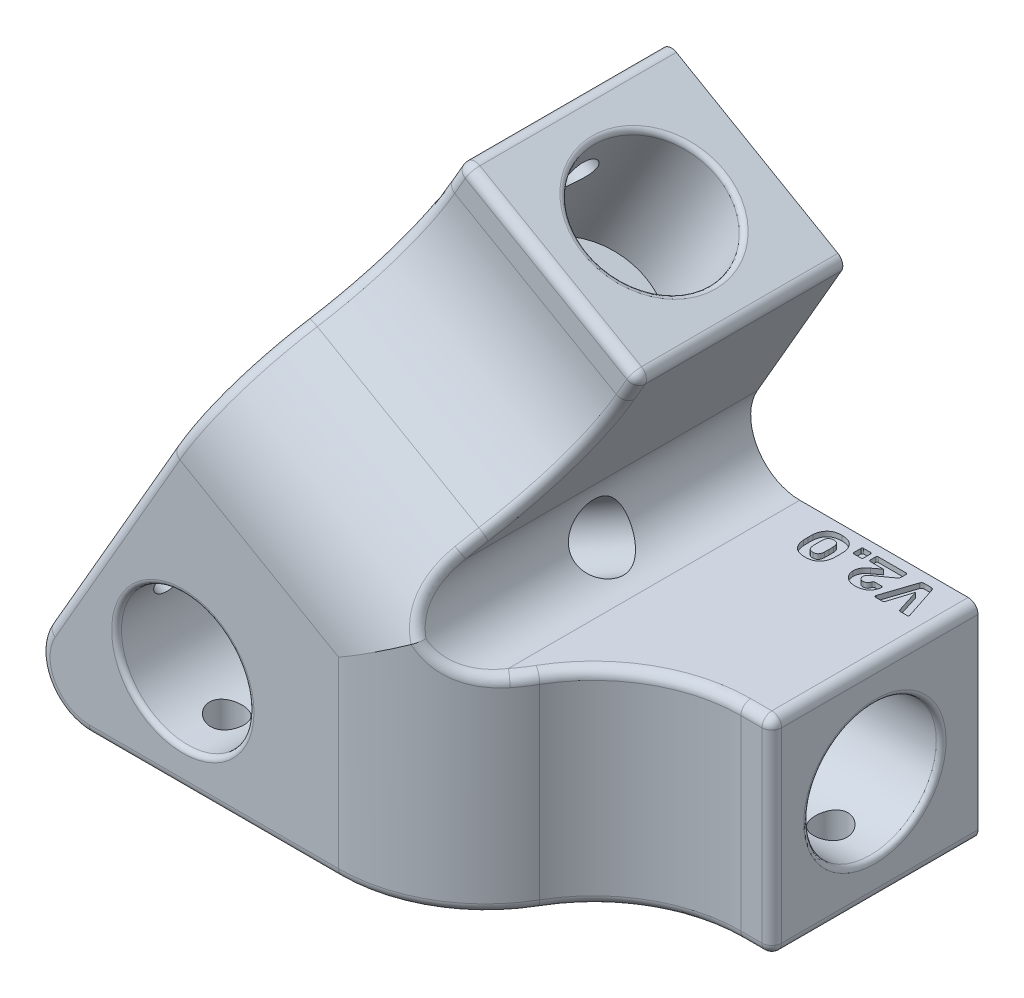
SolidWorks part; units mm, degrees
other "Corner Joint"
ref_plane "Front Plane" through (0, 0, 0) normal (0, 0, 1) x (1, 0, 0)
ref_plane "Top Plane" through (0, 0, 0) normal (0, 1, 0) x (1, 0, 0)
ref_plane "Right Plane" through (0, 0, 0) normal (1, 0, 0) x (0, 0, -1)
sketch "Sketch1" plane through (0, 0, 0) normal (0, 0, 1) x (1, 0, 0)
  line L0 (0, 0) -> (45, 0) construction
  line L1 (0, 0) -> (22.5, 38.9711) construction
  line L16 (45, -10.5) -> (-9.5263, -10.5)
  line L17 (16.8708, 42.2211) -> (28.1292, 35.7211) construction
  line L18 (16.8708, 42.2211) -> (9.3708, 29.2308) construction
  line L19 (9.3708, 29.2308) -> (20.6292, 22.7308) construction
  line L20 (28.1292, 35.7211) -> (20.6292, 22.7308) construction
  line L21 (30, 6.5) -> (45, 6.5) construction
  line L22 (30, 6.5) -> (30, -6.5) construction
  line L23 (30, -6.5) -> (45, -6.5) construction
  line L24 (45, 6.5) -> (45, -6.5) construction
  line L25 (-13.8564, -3) -> (13.4067, 44.2211)
  line L26 (13.4067, 44.2211) -> (31.5933, 33.7211)
  line L27 (31.5933, 33.7211) -> (22.5167, 18)
  line L28 (26.8468, 10.5) -> (45, 10.5)
  line L29 (45, 10.5) -> (45, -10.5)
  circle A0 centre (0, 0) radius 6.5 construction
  arc A1 (26.8468, 10.5) -> (22.5167, 18) centre (26.8468, 15.5) cw
  arc A2 (-9.5263, -10.5) -> (-13.8564, -3) centre (-9.5263, -5.5) cw
  point P2 (22.5, 38.9711)
  point P12 (45, 0)
  dimension "D7" = 15
  dimension "D8" = 13
  dimension "D13" = 5
  dimension "D1" = 60
  dimension "D2" = 45
  dimension "D3" = 45
  dimension "D4" = 13
  dimension "D5" = 15
  dimension "D6" = 13
  dimension "D9" = 4
  dimension "D10" = 4
  dimension "D11" = 4
  dimension "D12" = 4
extrude "Boss-Extrude3" add sketch "Sketch1" along normal blind 21
sketch "Sketch3" plane through (0, 0, 21) normal (0, 0, 1) x (1, 0, 0)
  line L0 (22.5167, 18) -> (4.3301, 28.5)
  line L1 (-13.8564, -3) -> (13.4067, 44.2211) construction
  line L2 (26.8468, 10.5) -> (26.8468, -10.5)
  line L3 (45, -10.5) -> (-9.5263, -10.5) construction
  line L4 (13.4067, 44.2211) -> (31.5933, 33.7211) construction
  line L5 (4.3301, 28.5) -> (-13.8564, -3)
  line L6 (-9.5263, -10.5) -> (26.8468, -10.5)
  line L7 (26.8468, 10.5) -> (26.6736, 10.5)
  line L8 (22.4301, 17.85) -> (22.5167, 18)
  line L9 (31.5933, 33.7211) -> (22.5167, 18) construction
  line L10 (26.8468, 10.5) -> (45, 10.5) construction
  circle A0 centre (0, 0) radius 6.75
  arc A1 (-9.5263, -10.5) -> (-13.8564, -3) centre (-9.5263, -5.5) cw
  arc A3 (22.5167, 18) -> (26.8468, 10.5) centre (26.8468, 15.5) ccw
  arc M12 (26.8468, 10.5) -> (22.5167, 18) centre (26.8468, 15.5) cw
  line M15 (13.4067, 44.2211) -> (-13.8564, -3)
  arc M16 (-13.8564, -3) -> (-9.5263, -10.5) centre (-9.5263, -5.5) ccw
  line M17 (-9.5263, -10.5) -> (45, -10.5)
  dimension "D1" = 5
  dimension "D2" = 13.5
extrude "Boss-Extrude4" add sketch "Sketch3" along normal blind 15 contours L2 L0 A0 M12 M15 M16 M17 region at (9.2242, 5.3256, 21)
sketch "Sketch4" plane through (45, 0, 0) normal (1, 0, 0) x (0, 0, -1)
  line L0 (-21, -10.5) -> (-21, 10.5) construction
  line L1 (-21, -10.5) -> (0, -10.5) construction
  circle A0 centre (-10.5, 0) radius 6.75
  dimension "D1" = 13.5
  dimension "D2" = 10.5
  dimension "D3" = 10.5
extrude "Cut-Extrude1" cut sketch "Sketch4" against normal blind 15
sketch "Sketch5" plane through (22.5, 38.9711, 0) normal (0.5, 0.866, 0) x (0.866, -0.5, 0)
  line L0 (-10.5, -21) -> (-10.5, 0) construction
  line L1 (10.5, 0) -> (-10.5, 0) construction
  circle A0 centre (0, -10.5) radius 6.75
  dimension "D1" = 13.5
  dimension "D2" = 10.5
  dimension "D3" = 10.5
extrude "Cut-Extrude2" cut sketch "Sketch5" against normal blind 15
fillet "Fillet1" radius 15 2 edges at (13.4234, 23.25, 21) (26.8468, 0, 21)
fillet "Fillet2" radius 15 2 edges at (26.8468, 0, 36) (13.4234, 23.25, 36)
fillet "Fillet3" radius 1 23 edges at (24.1108, 11.315, 33.5309) (27.9284, 10.5, 29.9162) (43.4234, 10.5, 21) (30.805, 32.3558, 21) (21.8979, 16.2133, 32.906) (23.0575, 18.9367, 29.9162) (43.4234, -10.5, 21) (34.3468, -10.5, 23.0096) (23.366, -10.5, 33.9904) (3.1699, -10.5, 36) (-13.8564, -8, 36) (-7.5083, 7.9952, 36) (2.5897, 25.4856, 33.9904) (12.6184, 42.8558, 21) (45, -10.5, 10.5) (45, 10.5, 10.5) (45, 0, 21) (34.3468, 10.5, 23.0096) (31.5933, 33.7211, 10.5) (22.5, 38.9711, 21) (26.2667, 24.4952, 23.0096) (8.0801, 34.9952, 23.0096) (13.4067, 44.2211, 10.5)
fillet "Fillet4" radius 0.5 3 edges at (45, 6.75, 10.5) (16.6543, 42.3461, 10.5) (6.75, 0, 36)
sketch "Sketch7" plane through (0, -10.5, 0) normal (0, -1, 0) x (1, 0, 0)
  line L0 (45, 20) -> (45, 0) construction
  line L1 (-9.5263, 36) -> (15.866, 36) construction
  line L2 (-14.5263, 35) -> (-14.5263, 0) construction
  circle A0 centre (40, 10) radius 1.75
  circle A1 centre (-0.5263, 31) radius 1.75
  point P4 (45, 10)
  dimension "D1" = 3.5
  dimension "D2" = 5
  dimension "D3" = 5
  dimension "D4" = 14
extrude "Cut-Extrude4" cut sketch "Sketch7" against normal blind 14
sketch "Sketch8" plane through (-9.0933, 5.25, 0) normal (-0.866, 0.5, 0) x (0, 0, 1)
  line L0 (0, 45) -> (20, 45) construction
  line L1 (0, -14.5263) -> (35, -14.5263) construction
  line L2 (36, -13.5263) -> (36, -9.5263) construction
  circle A0 centre (10, 40) radius 1.75
  circle A1 centre (31, -0.5263) radius 1.75
  point P5 (10, 45)
  dimension "D1" = 3.5
  dimension "D2" = 5
  dimension "D3" = 14
  dimension "D4" = 5
extrude "Cut-Extrude5" cut sketch "Sketch8" against normal blind 10
sketch "Sketch9" plane through (0, 0, 36) normal (0, 0, 1) x (1, 0, 0)
  line L0 (-4.0981, 1.0981) -> (-1.0981, -4.0981)
  line L1 (-1.0981, -4.0981) -> (4.0981, -1.0981)
  line L2 (4.0981, -1.0981) -> (1.0981, 4.0981)
  line L3 (1.0981, 4.0981) -> (-4.0981, 1.0981)
  line L4 (21.9582, 12.6776) -> (15.866, 9.1603) construction
  dimension "D1" = 6
  dimension "D2" = 6
  dimension "D3" = 3
  dimension "D4" = 3
extrude "Cut-Extrude6" cut sketch "Sketch9" against normal offset from surface (23 mm away) 8 up to face at (6.75, 0, 21) offset beyond the face yes
sketch "Sketch10" plane through (-2.5981, -1.5, 0) normal (0.866, 0.5, 0) x (0, 0, -1)
  line L0 (-13, 3) -> (-13, -3) construction
  line L1 (-21, -3) -> (-21, 3) construction
  line L2 (-13, 3) -> (-21, 3) construction
  circle A0 centre (-16, 0) radius 3
  point P6 (-21, 0)
  dimension "D1" = 6
  dimension "D2" = 3
extrude "Cut-Extrude7" cut sketch "Sketch10" along normal blind 40
fillet "Fillet5" radius 2 6 edges at (1.0981, 4.0981, 14.5) (4.0981, -1.0981, 18.5) (1.0981, 4.0981, 18.5) (4.0981, -1.0981, 14.5) (-1.0981, -4.0981, 17) (-4.0981, 1.0981, 17)
sketch "Sketch12" plane through (0, 10.5, 0) normal (0, 1, 0) x (1, 0, 0)
  line L0 (45, -1) -> (-14.5263, -1) construction
  line L1 (45, 0) -> (45, -20) construction
  line L2 (-14.5263, 0) -> (-14.5263, -35) construction
  line L3 (44, 0) -> (26.8468, 0) construction
  text T0 "  V2.0" font "Rubik" height in points 14
  dimension "D1" = 1
extrude "Cut-Extrude8" cut sketch "Sketch12" against normal blind 0.5
fillet "Fillet6" radius 2 8 edges at (-3.2979, 0.8837, 21) (-2.5981, -1.5, 21) (-0.8837, -3.2979, 21) (1.5, -2.5981, 21) (3.2979, -0.8837, 21) (2.5981, 1.5, 21) (0.8837, 3.2979, 21) (-1.5, 2.5981, 21)
